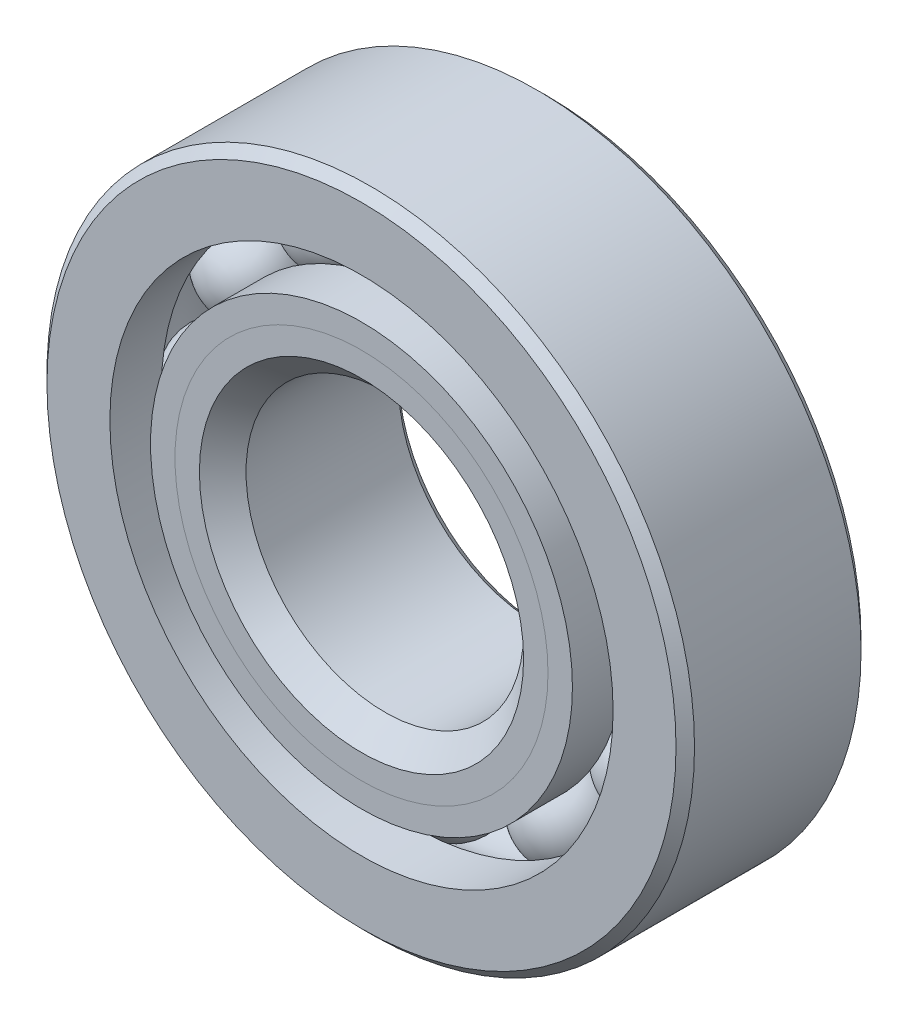
SolidWorks part; units mm, degrees
ref_plane "Front Plane" through (0, 0, 0) normal (0, 0, 1) x (1, 0, 0)
ref_plane "Top Plane" through (0, 0, 0) normal (0, 1, 0) x (1, 0, 0)
ref_plane "Right Plane" through (0, 0, 0) normal (1, 0, 0) x (0, 0, -1)
sketch "Sketch1" plane through (0, 0, 0) normal (1, 0, 0) x (0, 0, -1)
  line L0 (-4, 0) -> (4, 0) construction
  line L1 (0, 14) -> (0, -14) construction
  line L2 (3.6, 14) -> (-3.6, 14)
  line L3 (-3.6, 14) -> (-4, 13.6)
  line L4 (-4, 13.6) -> (-4, 10.8791)
  line L5 (-4, 10.8791) -> (-1.7778, 10.8791)
  line L6 (4, 10.8791) -> (1.7778, 10.8791)
  line L7 (4, 13.6) -> (4, 10.8791)
  line L8 (3.6, 14) -> (4, 13.6)
  line L9 (0, 14) -> (0, 10) construction
  line L10 (0, 10) -> (0, 6) construction
  line L11 (-4, -14) -> (4, -14) construction
  line L12 (0, -6) -> (0, 6) construction
  line L13 (4, -6) -> (4, 6) construction
  arc A0 (-1.7778, 10.8791) -> (1.7778, 10.8791) centre (0, 10) cw
  point P14 (0, 6)
  point P15 (0, -6)
  point P19 (0, -14)
  point P23 (0, 0)
  point P25 (4, 0)
  dimension "OD" = 28
  dimension "D1" = 45
  dimension "D2" = 0.4
  dimension "D3" = 3.5556
  dimension "D4" = 0.8791
  dimension "Width" = 8
  dimension "Shaft Dia" = 12
revolve "Revolve1" add sketch "Sketch1" angle 360 about L0
sketch "Sketch2" plane through (0, 0, 0) normal (1, 0, 0) x (0, 0, -1)
  line L0 (-4, 9.1209) -> (-1.7778, 9.1209)
  line L1 (-4, 13.6) -> (-4, -13.6) construction
  line L2 (-4, 9.1209) -> (-4, 8.0646)
  line L3 (-4, 8.0646) -> (-2.9437, 7.0084)
  line L4 (-2.9437, 7.0084) -> (0, 7.0084)
  line L5 (0, 14) -> (0, -14) construction
  line L6 (0, 7.0084) -> (0, 8.0167)
  line L7 (0, 8.0167) -> (0, 6) construction
  line L8 (-4, 9.1209) -> (-4, 7.0084) construction
  line L9 (-4, 7.0084) -> (-2.9437, 7.0084) construction
  arc A0 (-1.7778, 9.1209) -> (0, 8.0167) centre (0, 10) ccw
  arc A1 (1.7778, 10.8791) -> (-1.7778, 10.8791) centre (0, 10) ccw construction
  circle A2 centre (0, 10) radius 1.9833 construction
  dimension "D1" = 45
revolve "Revolve2" add sketch "Sketch2" angle 360 about L0
sketch "Sketch3" plane through (0, 0, 0) normal (1, 0, 0) x (0, 0, -1)
  line L0 (-4, 8.0646) -> (-2.9437, 7.0084)
  line L1 (-2.9437, 7.0084) -> (0, 7.0084)
  line L2 (0, 7.0084) -> (0, 8.0167)
  line L3 (-4, 8.0646) -> (-4, 7.0084)
  line L4 (-4, 9.1209) -> (-4, 7.0084) construction
  line L5 (-4, 7.0084) -> (-2.9916, 6)
  line L6 (-2.9916, 6) -> (3.6, 6)
  line L7 (3.6, 14) -> (3.6, -14) construction
  line L8 (3.6, 6) -> (4, 6.4)
  line L9 (4, -13.6) -> (4, 13.6) construction
  line L10 (4, 6.4) -> (4, 9.1209)
  line L11 (4, 9.1209) -> (1.7778, 9.1209)
  line L13 (3.6, 14) -> (4, 13.6) construction
  circle A0 centre (0, 10) radius 1.9833 construction
  arc A1 (1.7778, 9.1209) -> (0, 8.0167) centre (0, 10) cw
revolve "Revolve3" add sketch "Sketch3" angle 360 about L0
sketch "Sketch4" plane through (0, 0, 0) normal (1, 0, 0) x (0, 0, -1)
  line L0 (-1.9833, 10) -> (1.9833, 10)
  circle A1 centre (0, 10) radius 1.9833 construction
  arc A2 (-1.9833, 10) -> (1.9833, 10) centre (0, 10) cw
  arc A3 (1.7778, 10.8791) -> (-1.7778, 10.8791) centre (0, 10) ccw construction
revolve "Revolve4" add sketch "Sketch4" angle 360 about L0
ref_axis "Axis1" through (0, 0, -4) along (0, 0, 1)
pattern_circular "CirPattern1" count 12 every 30 about axis through (0, 0, -4) along (0, 0, 1) of bodies 104
sketch "REF" plane through (0, 0, 0) normal (1, 0, 0) x (0, 0, -1)
  line L0 (3.6, 6) -> (4, 6.4) construction
  line L1 (-2.9916, 6) -> (3.6, 6) construction
  line L2 (-4, 7.0084) -> (-2.9916, 6) construction
  line L3 (3.6, 6) -> (4, 6.4) construction
  line L4 (-2.9916, 6) -> (3.6, 6) construction
  line L5 (-4, 7.0084) -> (-2.9916, 6) construction
  line L6 (-4, 0) -> (4, 0) construction
  line L7 (-4, 0) -> (4, 0) construction
  line L8 (3.6, -6) -> (4, -6.4) construction
  line L9 (-2.9916, -6) -> (3.6, -6) construction
  line L10 (-4, -7.0084) -> (-2.9916, -6) construction
ref_axis "Center Axis 1" through (0, 0, -3.6) along (0, 0, 1)
equation "\"D2@Sketch1\" = \"Width@Sketch1\"*.05"
equation "\"D3@Sketch1\" = \"Width@Sketch1\"/2.25"
equation "\"D4@Sketch1\" = (((\"OD@Sketch1\"-\"Width@Sketch1\")/2)/3.25)/3.5"
equation "\"D2@CirPattern1\" = 360/\"Balls@CirPattern1\""
